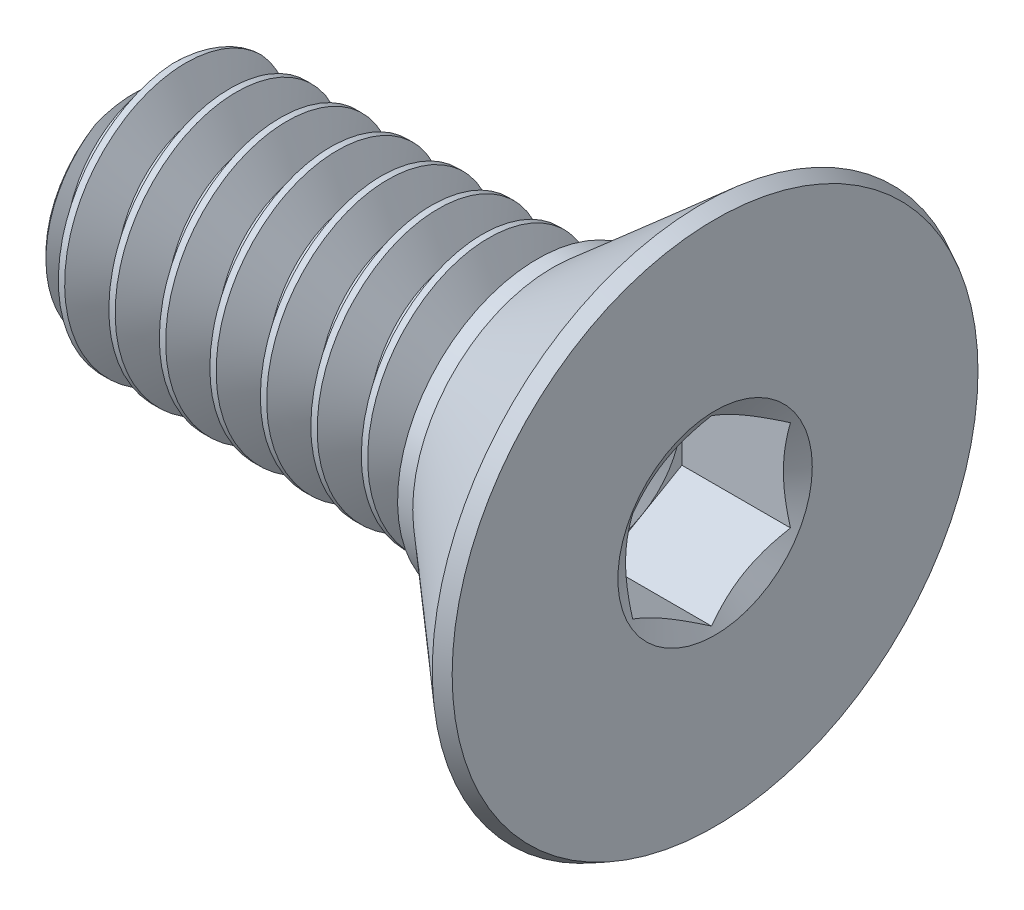
SolidWorks part; units mm, degrees
ref_plane "Front Plane" through (0, 0, 0) normal (0, 0, 1) x (1, 0, 0)
ref_plane "Top Plane" through (0, 0, 0) normal (0, 1, 0) x (1, 0, 0)
ref_plane "Right Plane" through (0, 0, 0) normal (1, 0, 0) x (0, 0, -1)
sketch "Sketch1" plane through (0, 0, 0) normal (0, 0, 1) x (1, 0, 0)
  line L0 (7.1438, 6.7818) -> (7.1438, -6.7818) construction
  line L1 (7.1438, 0) -> (-7.1438, 0) construction
  line L2 (-7.1437, 2.54) -> (-7.1437, -2.54) construction
  line L3 (-7.1437, 2.54) -> (-6.5088, 3.175) construction
  line L4 (-6.5088, 3.175) -> (3.0544, 3.175) construction
  line L8 (3.0544, 3.5146) -> (3.0544, -3.5146) construction
  line L9 (-7.1437, -2.54) -> (-6.5087, -3.175) construction
  line L10 (-6.5087, -3.175) -> (3.0544, -3.175) construction
  line L11 (3.0544, 3.5146) -> (6.2693, 6.3094) construction
  line L12 (3.0544, -3.5146) -> (6.2693, -6.3094) construction
  line L13 (6.6157, 6.096) -> (6.6157, -6.096) construction
  line L14 (3.0543, 3.4516) -> (3.1927, 3.4516) construction
  line L15 (3.1927, 3.4516) -> (3.1927, 3.3133) construction
  line L16 (7.1437, 1.9844) -> (4.3243, 1.9844) construction
  line L17 (4.3243, 1.9844) -> (4.3243, -1.9844) construction
  line L18 (4.3243, -1.9844) -> (7.1438, -1.9844) construction
  line L19 (6.6157, -6.096) -> (6.6157, -6.7818) construction
  line L20 (6.6157, 6.096) -> (6.6157, 6.7818) construction
  arc A0 (6.2693, 6.3094) -> (7.1438, 5.9109) centre (6.6157, 5.9109) cw construction
  arc A1 (6.2693, -6.3094) -> (7.1438, -5.9109) centre (6.6157, -5.9109) ccw construction
  arc A2 (3.0543, 3.4516) -> (3.1019, 3.556) centre (3.1927, 3.4516) cw construction
  arc A3 (3.0544, -3.4516) -> (3.1019, -3.556) centre (3.1927, -3.4516) ccw construction
  arc A4 (2.916, 3.175) -> (3.0544, 3.3133) centre (2.916, 3.3133) ccw construction
  point P10 (-5.8738, -3.175)
  point P13 (3.0544, 0)
  point P18 (6.6157, 0)
  point P19 (6.6157, -6.4389)
  point P37 (4.3243, 0)
  point P38 (-4.6037, -3.175)
  point P40 (6.6157, 6.4389)
  dimension "Head Diameter" = 13.5636
  dimension "End Chamfer Angle" = 45
  dimension "Screw Size Decimal Equivalent" = 6.35
  dimension "Chamfer Length" = 0.635
  dimension "Thread Pitch" = 1.27
  dimension "Head Height" = 4.0894
  dimension "Countersink Angle" = 82
  dimension "A Head Diameter Min" = 12.192
  dimension "F Fillet Transition Dia" = 7.112
  dimension "Length" = 14.2875
  dimension "Drive Size" = 3.9688
  dimension "T Key Engagement" = 2.8194
  dimension "Thread Note" = 2.54
sketch "Sketch2" plane through (0, 0, 0) normal (1, 0, 0) x (0, 0, -1)
  line L0 (0, 6.7818) -> (0, -6.7818) construction
  line L1 (0, 2.2914) -> (-1.9844, 1.1457) construction
  line L2 (-1.9844, 1.1457) -> (-1.9844, -1.1457) construction
  line L3 (-1.9844, -1.1457) -> (0, -2.2914) construction
  line L4 (0, -2.2914) -> (1.9844, -1.1457) construction
  line L5 (1.9844, -1.1457) -> (1.9844, 1.1457) construction
  line L6 (1.9844, 1.1457) -> (0, 2.2914) construction
  circle A0 centre (0, 0) radius 6.4389 construction
  circle A1 centre (0, 0) radius 1.9844 construction
  circle A2 centre (0, 0) radius 6.7818 construction
sketch "Sketch3" plane through (0, 0, 0) normal (0, 0, 1) x (1, 0, 0)
  line L0 (-6.5088, 3.175) -> (-7.1437, 2.54)
  line L1 (-7.1437, 2.54) -> (-7.1438, 0)
  line L2 (-7.1438, 0) -> (7.1438, 0)
  line L3 (7.1438, 0) -> (7.1438, 6.6123)
  line L5 (6.8128, 6.7818) -> (3.0544, 3.5146)
  line L7 (3.0544, 3.5146) -> (3.0544, 3.3133)
  line L9 (2.916, 3.175) -> (-6.5088, 3.175)
  line L10 (6.8128, 6.7818) -> (7.1438, 6.6123)
  line L11 (7.1438, 6.7818) -> (7.1438, -6.7818) construction
  line L12 (3.0544, 3.5146) -> (6.2693, 6.3094) construction
  arc A2 (3.0544, 3.3133) -> (2.916, 3.175) centre (2.916, 3.3133) cw
  dimension "D1" = 6.6123
revolve "Revolve1" add sketch "Sketch3" angle 360 about L1
sketch "Sketch4" plane through (7.1438, 0, 0) normal (1, 0, 0) x (0, 0, -1)
  line L1 (0, 2.2914) -> (-1.9844, 1.1457)
  line L2 (-1.9844, 1.1457) -> (-1.9844, -1.1457)
  line L3 (-1.9844, -1.1457) -> (0, -2.2914)
  line L4 (0, -2.2914) -> (1.9844, -1.1457)
  line L5 (1.9844, -1.1457) -> (1.9844, 1.1457)
  line L6 (1.9844, 1.1457) -> (0, 2.2914)
  circle A0 centre (0, 0) radius 1.9844 construction
extrude "Cut-Extrude1" cut sketch "Sketch4" against normal up to vertex (2.8194 mm away) up to point (4.3243, 1.9844, 0)
sketch "Sketch5" plane through (7.1438, 0, 0) normal (1, 0, 0) x (0, 0, -1)
  line L0 (0, 2.2914) -> (0, 2.4449) construction
  line L1 (0, 2.2914) -> (0, 2.1379) construction
  line L2 (0, 2.1379) -> (0, 1.9844) construction
  circle A0 centre (0, 0) radius 2.4449
  circle A2 centre (0, 0) radius 1.9844 construction
extrude "Cut-Extrude2" cut sketch "Sketch5" against normal through all draft 60
sketch "Sketch6" plane through (4.3243, 0, 0) normal (1, 0, 0) x (0, 0, -1)
  circle A0 centre (0, 0) radius 1.9844
  circle A1 centre (0, 0) radius 1.9844 construction
extrude "Cut-Extrude3" cut sketch "Sketch6" against normal through all draft 60
split "Split1" bodies to split 107 resulting bodies 108 109 split by face at (3.0544, 0, -3.3133)
sketch "Sketch7" plane through (0, 0, 0) normal (0, 0, 1) x (1, 0, 0)
  line L0 (-7.6994, -2.2126) -> (-8.255, -3.175) construction
  line L1 (-8.255, -3.175) -> (-7.1437, -3.175) construction
  line L2 (-7.1437, -3.175) -> (-7.6994, -2.2126) construction
  line L3 (-7.1437, -3.175) -> (-7.0644, -3.3125) construction
  line L4 (-7.0644, -3.3125) -> (-8.3344, -3.3125) construction
  line L5 (-8.3344, -3.3125) -> (-8.255, -3.175) construction
  line L6 (-7.7787, -2.3501) -> (-7.62, -2.3501) construction
  line L7 (-7.6994, -3.175) -> (-7.6994, -3.3125) construction
  line L8 (-7.6994, -2.2126) -> (-7.6994, -2.3501) construction
  line L9 (-7.1437, 2.54) -> (-7.1437, -2.54) construction
  line L10 (-6.5087, -3.175) -> (3.0544, -3.175) construction
  line L11 (-7.7787, -2.3501) -> (-8.2947, -3.2437)
  line L12 (-8.2947, -3.2437) -> (-7.1041, -3.2437)
  line L13 (-7.1041, -3.2437) -> (-7.62, -2.3501)
  line L14 (-7.62, -2.3501) -> (-7.7787, -2.3501)
  dimension "D1" = 1.27
  dimension "D2" = 0.1588
sketch "Sketch8" plane through (-7.1438, 0, 0) normal (-1, 0, 0) x (0, 0, 1)
  line L0 (0, 2.54) -> (0, -2.54) construction
  circle A0 centre (0, 0) radius 3.175
curve "Helix/Spiral1" pitch 1.27 height 14.2875 radius 3.175 centre (-7.1438, 0, 0) axis (1, 0, 0) start towards (0, 0, 1)
sweep "Cut-Sweep1" cut profiles "Sketch7" path "Helix/Spiral1" align with end faces yes
sketch "Sketch11" plane through (3.0544, 0, 0) normal (-1, 0, 0) x (0, 0, 1)
  circle A0 centre (0, 0) radius 3.5146 construction
  circle A1 centre (0, 0) radius 3.5146
extrude "Boss-Extrude1" add sketch "Sketch11" along normal blind 0.381
sketch "Sketch12" plane through (2.6734, 0, 0) normal (-1, 0, 0) x (0, 0, 1)
  circle A1 centre (0, 0) radius 3.5146
  circle A3 centre (0, 0) radius 3.5146
  dimension "D1" = 0
extrude "Boss-Extrude2" add sketch "Sketch12" along normal through all draft 55
equation "\"Chamfer Length@Sketch1\" = \"Thread Pitch@Sketch1\" * .5"
equation "\"D1@Sketch7\"=\"Thread Pitch@Sketch1\""
equation "\"D2@Sketch7\"=\"D1@Sketch7\"/8"
equation "\"D4@Helix/Spiral1\"=\"Thread Pitch@Sketch1\""
equation "\"D3@Helix/Spiral1\" = \"Length@Sketch1\""
equation "\"Thread Note@Sketch1\" = \"Thread Pitch@Sketch1\" * 2"
equation "\"D1@Sketch3\"=\"Head Diameter@Sketch1\"*0.975*0.5"
